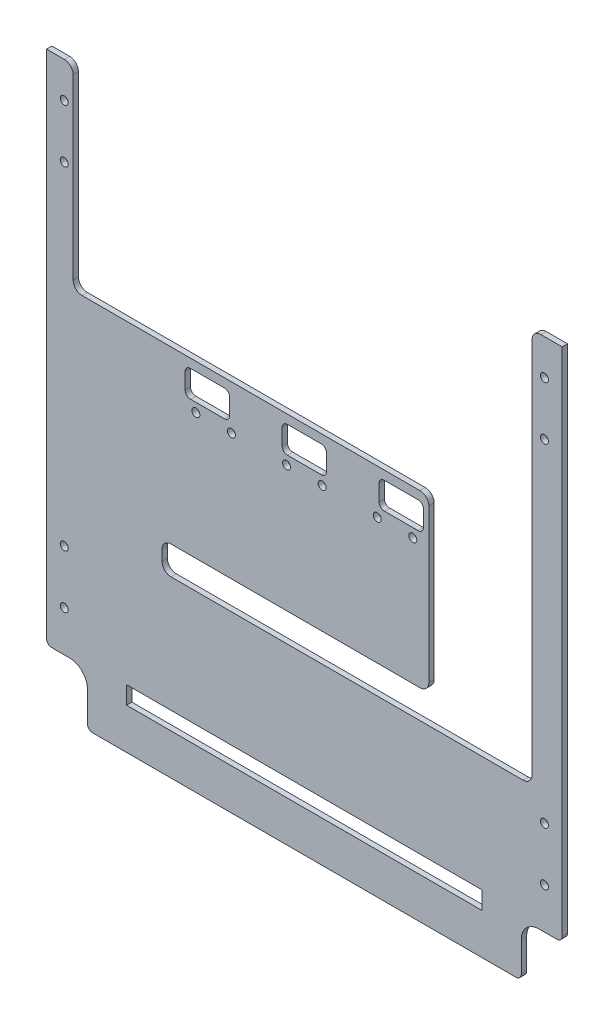
SolidWorks part; units mm, degrees
ref_plane "Front" through (0, 0, 0) normal (0, 0, 1) x (1, 0, 0)
ref_plane "Top" through (0, 0, 0) normal (0, 1, 0) x (1, 0, 0)
ref_plane "Right" through (0, 0, 0) normal (1, 0, 0) x (0, 0, -1)
sketch "Esquisse1" plane through (0, 0, 0) normal (0, 0, 1) x (1, 0, 0)
  line L1 (0, 0) -> (290, 0)
  line L2 (0, 0) -> (0, 320)
  line L3 (0, 320) -> (290, 320)
  line L4 (290, 0) -> (290, 320)
  dimension "D1" = 290
  dimension "D2" = 320
extrude "Boss.-Extru.1" add sketch "Esquisse1" along normal blind 3
sketch "Esquisse2" plane through (0, 0, 3) normal (0, 0, 1) x (1, 0, 0)
  line L0 (145, 0) -> (145, 56.1801) construction
  line L1 (290, 0) -> (267, 0)
  line L2 (290, 0) -> (290, 30)
  line L3 (290, 30) -> (267, 30)
  line L4 (267, 0) -> (267, 30)
  line L5 (0, 0) -> (290, 0) construction
  line L6 (23, 0) -> (23, 30)
  line L7 (0, 30) -> (23, 30)
  line L8 (0, 0) -> (0, 30)
  line L9 (0, 0) -> (23, 0)
  dimension "D1" = 23
  dimension "D2" = 30
extrude "Enlèv. mat.-Extru.1" cut sketch "Esquisse2" against normal through all both and the other way through all
fillet "Congé1" radius 10 2 edges at (267, 30, 1.5) (23, 30, 1.5)
fillet "Congé2" radius 3 4 edges at (290, 30, 1.5) (0, 30, 1.5) (23, 0, 1.5) (267, 0, 1.5)
sketch "Esquisse3" plane through (0, 0, 3) normal (0, 0, 1) x (1, 0, 0)
  line L0 (290, 320) -> (0, 320) construction
  line L1 (75, 320) -> (215, 320)
  line L2 (75, 320) -> (75, 210)
  line L3 (75, 210) -> (215, 210)
  line L4 (215, 320) -> (215, 210)
  line L5 (145, 210) -> (145, 0) construction
  line L6 (26, 0) -> (264, 0) construction
  dimension "D1" = 140
  dimension "D2" = 110
extrude "Enlèv. mat.-Extru.2" cut sketch "Esquisse3" against normal through all both and the other way through all
sketch "Esquisse4" plane through (0, 0, 3) normal (0, 0, 1) x (1, 0, 0)
  line L0 (290, 320) -> (215, 320) construction
  line L1 (215, 320) -> (273, 320)
  line L2 (215, 320) -> (215, 98)
  line L3 (215, 98) -> (273, 98)
  line L4 (273, 320) -> (273, 98)
  line L5 (290, 33) -> (290, 320) construction
  line L6 (215, 320) -> (215, 210) construction
  line L7 (26, 0) -> (264, 0) construction
  dimension "D1" = 17
  dimension "D2" = 98
extrude "Enlèv. mat.-Extru.3" cut sketch "Esquisse4" against normal through all both and the other way through all
sketch "Esquisse5" plane through (0, 0, 3) normal (0, 0, 1) x (1, 0, 0)
  line L0 (75, 320) -> (0, 320) construction
  line L1 (75, 210) -> (15, 210)
  line L2 (75, 210) -> (75, 320)
  line L3 (75, 320) -> (15, 320)
  line L4 (15, 210) -> (15, 320)
  line L5 (0, 320) -> (0, 33) construction
  dimension "D1" = 15
extrude "Enlèv. mat.-Extru.4" cut sketch "Esquisse5" against normal through all both and the other way through all
sketch "Esquisse6" plane through (0, 0, 3) normal (0, 0, 1) x (1, 0, 0)
  line L0 (215, 98) -> (215, 210) construction
  line L1 (215, 98) -> (65, 98)
  line L2 (215, 98) -> (215, 114)
  line L3 (215, 114) -> (65, 114)
  line L4 (65, 98) -> (65, 114)
  line L5 (26, 0) -> (264, 0) construction
  line L6 (0, 320) -> (0, 33) construction
  dimension "D1" = 16
  dimension "D2" = 98
  dimension "D3" = 65
extrude "Enlèv. mat.-Extru.5" cut sketch "Esquisse6" against normal through all both and the other way through all
fillet "Congé3" radius 5 8 edges at (273, 98, 1.5) (65, 98, 1.5) (65, 114, 1.5) (215, 114, 1.5) (215, 210, 1.5) (15, 210, 1.5) (273, 320, 1.5) (15, 320, 1.5)
sketch "Esquisse7" plane through (0, 0, 3) normal (0, 0, 1) x (1, 0, 0)
  line L0 (280, 320) -> (280, 300) construction
  line L1 (290, 320) -> (278, 320) construction
  line L2 (273, 315) -> (273, 103) construction
  line L3 (280, 300) -> (280, 270) construction
  line L4 (145, 0) -> (145, 300) construction
  line L5 (26, 0) -> (264, 0) construction
  line L6 (10, 300) -> (10, 270) construction
  line L7 (10, 320) -> (10, 300) construction
  line L8 (0, 176.5) -> (290, 176.5) construction
  line L9 (0, 320) -> (0, 33) construction
  line L10 (290, 33) -> (290, 320) construction
  line L11 (280, 53) -> (280, 83) construction
  line L12 (280, 33) -> (280, 53) construction
  line L13 (10, 33) -> (10, 53) construction
  line L14 (10, 53) -> (10, 83) construction
  circle A0 centre (280, 300) radius 2.25
  circle A1 centre (280, 270) radius 2.25
  circle A2 centre (10, 270) radius 2.25
  circle A3 centre (10, 300) radius 2.25
  circle A4 centre (280, 83) radius 2.25
  circle A5 centre (280, 53) radius 2.25
  circle A6 centre (10, 53) radius 2.25
  circle A7 centre (10, 83) radius 2.25
  dimension "D2" = 4.5
  dimension "D4" = 30
  dimension "D1" = 7
  dimension "D3" = 20
extrude "Enlèv. mat.-Extru.6" cut sketch "Esquisse7" against normal through all both and the other way through all
sketch "Esquisse8" plane through (0, 0, 3) normal (0, 0, 1) x (1, 0, 0)
  line L0 (145, 0) -> (145, 158.346) construction
  line L1 (26, 0) -> (264, 0) construction
  line L2 (210, 210) -> (20, 210) construction
  line L3 (186, 185) -> (206, 185) construction
  line L4 (155, 185) -> (186, 185) construction
  line L5 (104, 185) -> (84, 185) construction
  circle A0 centre (135, 185) radius 2.25
  circle A1 centre (155, 185) radius 2.25
  circle A2 centre (186, 185) radius 2.25
  circle A3 centre (206, 185) radius 2.25
  circle A4 centre (84, 185) radius 2.25
  circle A5 centre (104, 185) radius 2.25
  dimension "D1" = 4.5
  dimension "D2" = 20
  dimension "D3" = 25
  dimension "D4" = 20
  dimension "D5" = 41
extrude "Enlèv. mat.-Extru.7" cut sketch "Esquisse8" against normal through all both and the other way through all
sketch "Esquisse9" plane through (0, 0, 3) normal (0, 0, 1) x (1, 0, 0)
  line L0 (135, 185) -> (155, 185) construction
  line L1 (132.5, 205) -> (157.5, 205)
  line L2 (132.5, 205) -> (132.5, 190)
  line L3 (132.5, 190) -> (157.5, 190)
  line L4 (157.5, 205) -> (157.5, 190)
  line L5 (145, 185) -> (145, 205) construction
  line L6 (155, 185) -> (172.25, 185) construction
  line L7 (172.25, 185) -> (172.25, 205) construction
  line L8 (187, 205) -> (187, 190)
  line L9 (212, 190) -> (187, 190)
  line L10 (212, 205) -> (212, 190)
  line L11 (212, 205) -> (187, 205)
  line L12 (186, 185) -> (186, 194.1597) construction
  line L13 (104, 185) -> (104, 194.1597) construction
  line L14 (78, 205) -> (103, 205)
  line L15 (78, 205) -> (78, 190)
  line L16 (78, 190) -> (103, 190)
  line L17 (103, 205) -> (103, 190)
  dimension "D1" = 25
  dimension "D2" = 15
  dimension "D3" = 20
  dimension "D4" = 26
extrude "Enlèv. mat.-Extru.8" cut sketch "Esquisse9" against normal through all both and the other way through all
fillet "Congé4" radius 3 12 edges at (157.5, 190, 1.5) (157.5, 205, 1.5) (132.5, 205, 1.5) (132.5, 190, 1.5) (212, 190, 1.5) (212, 205, 1.5) (187, 205, 1.5) (187, 190, 1.5) (103, 190, 1.5) (103, 205, 1.5) (78, 205, 1.5) (78, 190, 1.5)
sketch "Esquisse10" plane through (0, 0, 3) normal (0, 0, 1) x (1, 0, 0)
  line L0 (145, 0) -> (145, 23) construction
  line L1 (45, 33) -> (245, 33)
  line L2 (45, 33) -> (45, 23)
  line L3 (45, 23) -> (245, 23)
  line L4 (245, 33) -> (245, 23)
  line L5 (26, 0) -> (264, 0) construction
  dimension "D1" = 10
  dimension "D2" = 23
  dimension "D3" = 200
extrude "Enlèv. mat.-Extru.9" cut sketch "Esquisse10" against normal through all both and the other way through all
